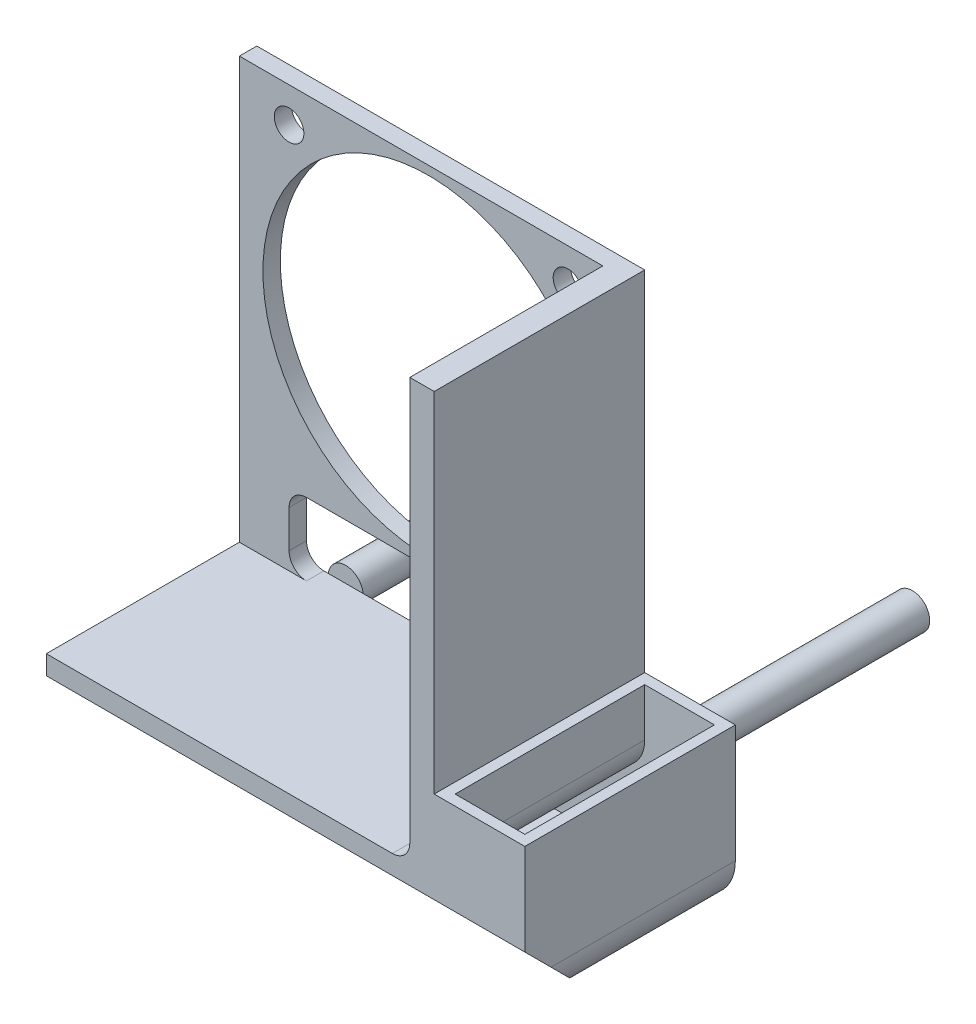
SolidWorks part; units mm, degrees
ref_plane "Front" through (0, 0, 0) normal (0, 0, 1) x (1, 0, 0)
ref_plane "Top" through (0, 0, 0) normal (0, 1, 0) x (1, 0, 0)
ref_plane "Right" through (0, 0, 0) normal (1, 0, 0) x (0, 0, -1)
sketch "Sketch1" plane through (0, 0, 0) normal (0, 0, 1) x (1, 0, 0)
  line L1 (0, 0) -> (40, 0)
  line L2 (0, 0) -> (0, 40)
  line L3 (0, 40) -> (40, 40)
  line L4 (40, 0) -> (40, 40)
  line L5 (20, 40) -> (20, 0) construction
  line L6 (0, 20) -> (40, 20) construction
  point P204 (20, 20)
  dimension "D1" = 40
  dimension "D2" = 40
extrude "Boss-Extrude1" add sketch "Sketch1" along normal blind 2 contours L4 L3 L2 L1 | L4 | L4 region at (20, 20, 0)
hole_wizard "M3 Clearance Hole1" positions "Sketch2" profile "Sketch3" hole size "M3" standard "ANSI Metric" end condition through all
sketch "Sketch2" plane through (0, 0, 2) normal (0, 0, 1) x (1, 0, 0)
  line L4 (4, 36) -> (36, 4) construction
  line L5 (36, 4) -> (36, 36) construction
  line L6 (36, 36) -> (4, 4) construction
  line L8 (0, 20) -> (20, 20) construction
  line L9 (0, 0) -> (0, 40) construction
  line L11 (20, 20) -> (20, 40) construction
  line L12 (0, 40) -> (40, 40) construction
  point P0 (4, 36)
  point P2 (36, 4)
  point P12 (4, 4)
  point P14 (36, 36)
  dimension "D1" = 32
  dimension "D2" = 32
sketch "Sketch3" plane through (4, 36, 2) normal (1, 0, 0) x (0, -1, 0)
  line L0 (0, 0) -> (0, 2)
  line L1 (0, 2) -> (1.7, 2)
  line L2 (1.7, 2) -> (1.7, 0)
  line L5 (1.7, 0) -> (0, 0)
  line L11 (0, -6.35) -> (0, 107.95) construction
  dimension "Thru Hole Dia." = 3.4
  dimension "Thru Hole Depth" = 2
sketch "Sketch10" plane through (0, 0, 2) normal (0, 0, 1) x (1, 0, 0)
  line L1 (0, 0) -> (40, 0)
  line L2 (0, 0) -> (0, -8.3)
  line L3 (0, -8.3) -> (40, -8.3)
  line L4 (40, 0) -> (40, -8.3)
  dimension "D1" = 8.3
extrude "Boss-Extrude7" add sketch "Sketch10" against normal blind 2
sketch "Sketch20" plane through (0, 0, 0) normal (0, 0, -1) x (-1, 0, 0)
  line L0 (-37.5, -14.5) -> (-2.5, -14.5) construction
  line L1 (-20, -14.5) -> (-20, -8.3) construction
  line L2 (0, -8.3) -> (-40, -8.3) construction
  circle A0 centre (-37.5, -14.5) radius 2
  circle A1 centre (-2.5, -14.5) radius 2
  dimension "D3" = 4
  dimension "D1" = 35
  dimension "D2" = 14.5
extrude "Boss-Extrude10" add sketch "Sketch20" along normal blind 30 from offset 6 separate body
sketch "Sketch21" plane through (0, 0, 0) normal (0, 1, 0) x (1, 0, 0)
  line L0 (40, -2) -> (40, 0) construction
  line L1 (44, -22.95) -> (52, -22.95)
  line L2 (44, -22.95) -> (44, -1.2)
  line L3 (44, -1.2) -> (52, -1.2)
  line L4 (52, -22.95) -> (52, -1.2)
  line L8 (0, 0) -> (40, 0) construction
  dimension "D1" = 21.75
  dimension "D2" = 8
  dimension "D3" = 4
  dimension "D4" = 1.2
ref_plane "Plane1" through (0, 0, 22.95) normal (0, 0, -1) x (-1, 0, 0)
sketch "Sketch22" plane through (0, 0, 22.95) normal (0, 0, -1) x (-1, 0, 0)
  line L7 (-44, 0) -> (-52, 0)
  line L8 (-44, 0) -> (-52, 0) construction
  line L10 (-52, 0) -> (-52, -17.5)
  line L11 (-52, -17.5) -> (0.5, -17.5)
  line L12 (0.5, -17.5) -> (0.5, -9.5)
  line L13 (0.5, -9.5) -> (-44, -9.5)
  line L14 (-44, -9.5) -> (-44, 0)
  circle A6 centre (-37.5, -14.5) radius 2 construction
  circle A7 centre (-2.5, -14.5) radius 2 construction
  dimension "D2" = 3
  dimension "D1" = 3
  dimension "D3" = 8
extrude "Boss-Extrude11" add sketch "Sketch22" along normal blind 21.75 separate body
chamfer "Chamfer1" distance 7.5 angle 45 1 edges at (25.75, -17.5, 22.95)
fillet "Fillet1" radius 4 2 edges at (52, -17.5, 8.325) (44, -9.5, 12.075)
shell "Shell1" thickness 1.2 removed face at (48, 0, 12.075) outward yes
sketch "Sketch25" plane through (0, 0, 0) normal (0, 0, -1) x (-1, 0, 0)
  line L0 (-40, -8.3) -> (-40, 40) construction
  line L1 (-42.8, -8.3) -> (-40, -8.3)
  line L2 (-42.8, -8.3) -> (-42.8, 40)
  line L3 (-42.8, 40) -> (-40, 40)
  line L4 (-40, -8.3) -> (-40, 40)
  line L6 (0, 40) -> (-40, 40) construction
  point P7 (-40, 40)
  point P9 (0, 0)
extrude "Boss-Extrude14" add sketch "Sketch25" against normal up to surface (24.15 mm away) up to face at (32.74, -6.2391, 24.15)
sketch "Sketch26" plane through (0, 0, 2) normal (0, 0, 1) x (1, 0, 0)
  line L0 (0, -8.3) -> (0, 40) construction
  line L1 (40, -8.3) -> (4, -8.3)
  line L2 (40, -8.3) -> (40, 0)
  line L3 (40, 0) -> (4, 0)
  line L4 (4, -8.3) -> (4, 0)
  point P6 (40, -8.3)
  point P8 (6.2396, 0)
  dimension "D1" = 4
extrude "Cut-Extrude5" cut sketch "Sketch26" against normal through all
sketch "Sketch27" plane through (0, 0, 2) normal (0, 0, 1) x (1, 0, 0)
  line L0 (4, 36) -> (36, 4) construction
  circle A0 centre (20, 20) radius 19
  point P6 (20, 20)
  dimension "D1" = 38
extrude "Cut-Extrude6" cut sketch "Sketch27" against normal through all
fillet "Fillet2" radius 2 3 edges at (4, 0, 1) (4, -8.3, 1) (40, 0, 1)
fillet "Fillet3" radius 2 1 edges at (40, -8.3, 12.075)
sketch "Sketch29" plane through (0, 0, 2) normal (0, 0, 1) x (1, 0, 0)
  line L1 (0, 40) -> (-1.7, 40)
  line L2 (0, 40) -> (0, -8.3)
  line L3 (0, -8.3) -> (-1.7, -8.3)
  line L4 (-1.7, 40) -> (-1.7, -8.3)
extrude "Boss-Extrude15" add sketch "Sketch29" against normal up to surface (2 mm away) up to face at (39, 20, 0)
other "DeleteFace1" face at (5.7, 4, 0) and patch yes
